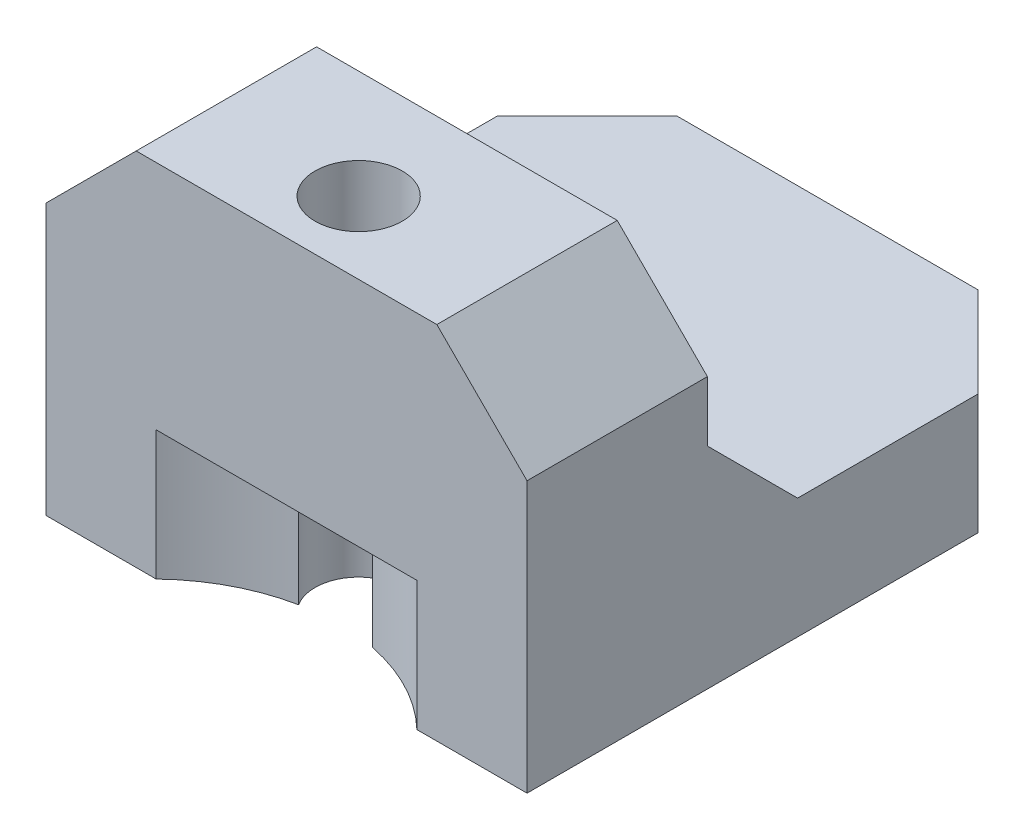
SolidWorks part; units mm, degrees
ref_plane "前视基准面" through (0, 0, 0) normal (0, 0, 1) x (1, 0, 0)
ref_plane "上视基准面" through (0, 0, 0) normal (0, 1, 0) x (1, 0, 0)
ref_plane "右视基准面" through (0, 0, 0) normal (1, 0, 0) x (0, 0, -1)
other "Configuration Table"
sketch "草图1" plane through (0, 0, 0) normal (0, 1, 0) x (1, 0, 0)
  line L1 (0, 0) -> (16, 0)
  line L2 (0, 0) -> (0, 18)
  line L3 (0, 18) -> (16, 18)
  line L4 (16, 0) -> (16, 18)
  dimension "D1" = 18
  dimension "D2" = 16
extrude "凸台-拉伸1" add sketch "草图1" along normal blind 4
sketch "草图2" plane through (0, 4, 0) normal (0, 1, 0) x (1, 0, 0)
  line L0 (16, 18) -> (0, 18) construction
  line L1 (0, 18) -> (0, 0) construction
  circle A0 centre (8, 10) radius 1.65
  dimension "D1" = 3.3
  dimension "D3" = 8
  dimension "D2" = 8
extrude "切除-拉伸1" cut sketch "草图2" against normal blind 4
sketch "草图3" plane through (0, 4, 0) normal (0, 1, 0) x (1, 0, 0)
  line L0 (16, 0) -> (16, 18) construction
  line L1 (0, 0) -> (16, 0)
  line L2 (0, 0) -> (0, 6)
  line L3 (0, 6) -> (16, 6)
  line L4 (16, 0) -> (16, 6)
  dimension "D1" = 6
extrude "凸台-拉伸2" add sketch "草图3" along normal blind 8
sketch "草图4" plane through (0, 12, 0) normal (0, 1, 0) x (1, 0, 0)
  line L0 (0, 0) -> (16, 0) construction
  line L1 (0, 6) -> (0, 0) construction
  circle A0 centre (8, 2.4) radius 1.45
  dimension "D1" = 2.9
  dimension "D2" = 2.4
  dimension "D3" = 8
extrude "切除-拉伸2" cut sketch "草图4" against normal through all
chamfer "倒角1" distance 3 angle 45 2 edges at (0, 2, -18) (16, 2, -18)
chamfer "倒角2" distance 3 angle 45 1 edges at (8, 4, -6)
chamfer "倒角3" distance 3 angle 45 2 edges at (0, 12, -3) (16, 12, -3)
sketch "草图6" plane through (0, 4, 0) normal (0, 1, 0) x (1, 0, 0)
  circle A0 centre (8, 10) radius 3
  dimension "D1" = 6
extrude "切除-拉伸3" cut sketch "草图6" along normal through all
sketch "草图7" plane through (0, 0, 0) normal (0, -1, 0) x (-1, 0, 0)
  line L0 (0, 0) -> (-16, 0) construction
  circle A0 centre (-8, -4.5) radius 6.25
  dimension "D2" = 12.5
  dimension "D1" = 4.5
extrude "切除-拉伸4" cut sketch "草图7" against normal blind 2.8
chamfer "倒角4" distance 1.5 angle 45 1 edges at (8, 2.8, 0)
